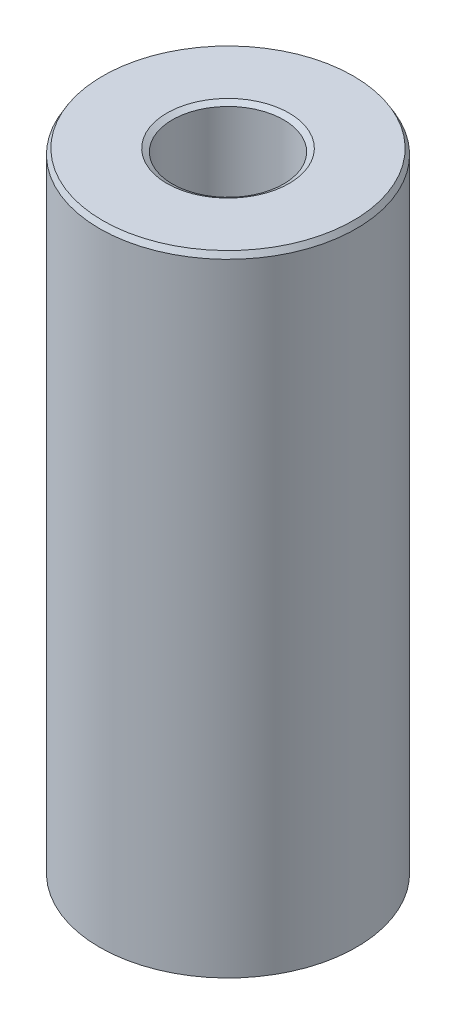
SolidWorks part; units mm, degrees
ref_plane "Front Plane" through (0, 0, 0) normal (0, 0, 1) x (1, 0, 0)
ref_plane "Top Plane" through (0, 0, 0) normal (0, 1, 0) x (1, 0, 0)
ref_plane "Right Plane" through (0, 0, 0) normal (1, 0, 0) x (0, 0, -1)
sketch "Sketch1" plane through (0, 0, 0) normal (0, 1, 0) x (1, 0, 0)
  circle A0 centre (0, 0) radius 45
  dimension "SLEEVE_OD" = 90
extrude "Boss-Extrude1" add sketch "Sketch1" along normal blind 221.1093
sketch "Sketch2" plane through (0, 0, 0) normal (0, 1, 0) x (1, 0, 0)
  circle A0 centre (0, 0) radius 19.503
  dimension "BORE_D" = 39.006
extrude "Cut-Extrude1" cut sketch "Sketch2" along normal through all
chamfer "Chamfer1" distance 1.8998 angle 30 4 edges at (0, 221.1093, 19.503) (0, 0, 19.503) (0, 0, 45) (0, 221.1093, 45) first distance on face at (0, 221.1093, 19.503) first distance on face at (0, 0, 19.503) first distance on face at (0, 221.1093, 45)
